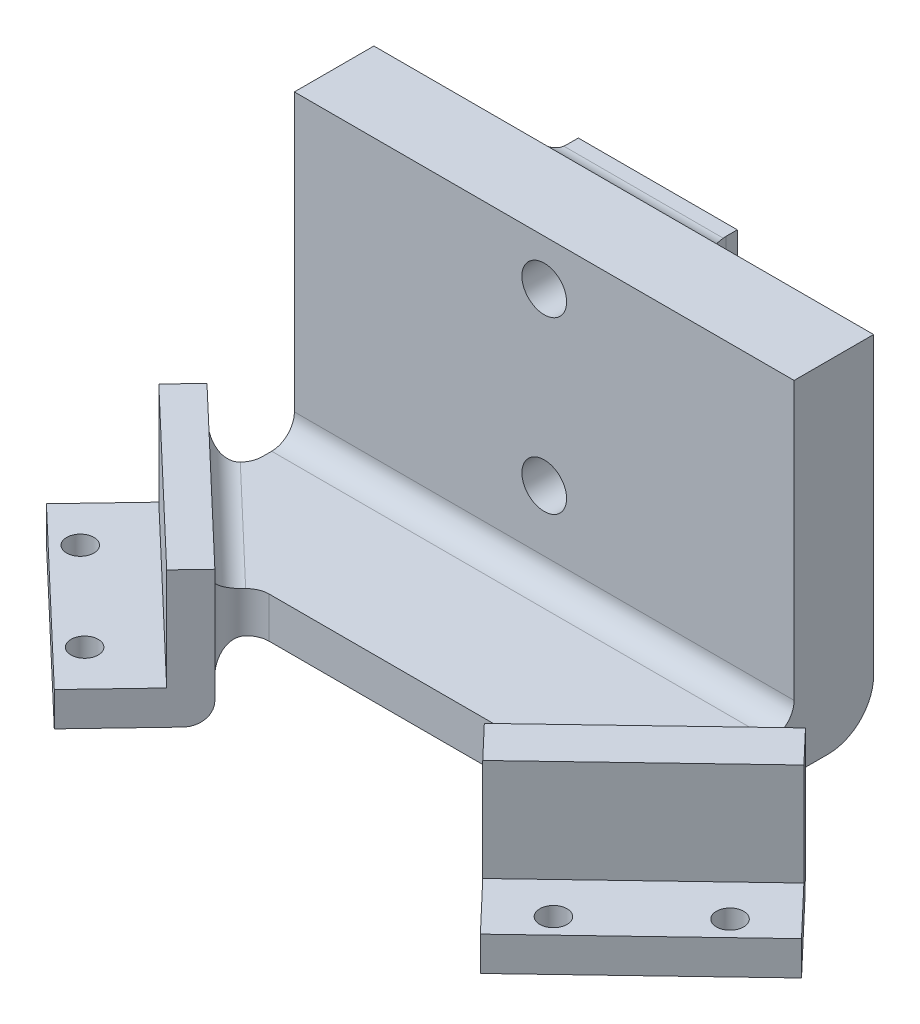
SolidWorks part; units mm, degrees
ref_plane "Front Plane" through (0, 0, 0) normal (0, 0, 1) x (1, 0, 0)
ref_plane "Top Plane" through (0, 0, 0) normal (0, 1, 0) x (1, 0, 0)
ref_plane "Right Plane" through (0, 0, 0) normal (1, 0, 0) x (0, 0, -1)
sketch "Sketch1" plane through (0, 0, 0) normal (0, 0, 1) x (1, 0, 0)
  line L0 (0, 89.7562) -> (0, -86.36) construction
  line L1 (27.94, 10.688) -> (-27.94, 10.688)
  line L2 (-27.94, 10.688) -> (-27.94, -27.412)
  line L3 (-27.94, -27.412) -> (27.94, -27.412)
  line L4 (27.94, 10.688) -> (27.94, -27.412)
  line L5 (-27.94, -22.84) -> (0, -22.84)
  line L6 (0, -22.84) -> (27.94, -22.84)
  line L7 (8.89, 9.3984) -> (-8.89, 9.3984)
  line L8 (-8.89, 9.3984) -> (-8.89, -19.8116)
  line L9 (-8.89, -19.8116) -> (8.89, -19.8116)
  line L10 (8.89, 9.3984) -> (8.89, -19.8116)
  line L11 (27.94, -22.84) -> (-27.94, -22.84) construction
  circle A0 centre (0, 5.5765) radius 2.5006
  circle A2 centre (0, -13.4735) radius 2.5006
  point P5 (-27.94, -8.362)
  point P7 (0, 10.688)
  point P8 (27.94, -8.362)
  point P11 (0, -27.412)
  point P19 (0, -19.8116)
  point P20 (0, 9.3984)
  dimension "D6" = 5.0013
  dimension "D7" = 5.0013
  dimension "D1" = 38.1
  dimension "D2" = 55.88
  dimension "D3" = 4.572
  dimension "D4" = 17.78
  dimension "D5" = 29.21
  dimension "D8" = 19.05
extrude "Boss-Extrude1" add sketch "Sketch1" along normal blind 8.89 contours L1 L0 L7 L10 L9 L6 L4 | L0 L1 L2 L5 L9 L8 L7 region at (17.623, -6.4095, 0) region at (-17.623, -6.4095, 0)
extrude "Boss-Extrude2" add sketch "Sketch1<3>" along normal blind 25.4 contours L6 L0 L3 L4 | L0 L5 L2 L3 region at (13.97, -25.126, 0) region at (-13.97, -25.126, 0)
sketch "Sketch1<3>" plane through (0, 0, 0) normal (0, 0, 1) x (1, 0, 0) same geometry as "Sketch1"
extrude "Boss-Extrude3" add sketch "Sketch1<4>" along normal blind 8.89 contours L0 L7 L8 L9 A2 A0 | L7 L0 A0 A2 L9 L10 region at (4.7219, -5.3095, 0) region at (-4.7219, -5.3095, 0)
sketch "Sketch1<4>" plane through (0, 0, 0) normal (0, 0, 1) x (1, 0, 0) same geometry as "Sketch1"
extrude "Boss-Extrude5" add sketch "Sketch1<5>" against normal blind 3.81 contours L0 L7 L8 L9 A2 A0 | L7 L0 A0 A2 L9 L10 region at (4.7219, -5.3095, 0) region at (-4.7219, -5.3095, 0)
sketch "Sketch1<5>" plane through (0, 0, 0) normal (0, 0, 1) x (1, 0, 0) same geometry as "Sketch1"
fillet "Fillet1" radius 2.54 1 edges at (0, 9.3984, 0)
fillet "Fillet7" radius 2.54 1 edges at (0, -19.8116, 0)
fillet "Fillet8" radius 2.54 1 edges at (-8.89, -5.8318, 0)
fillet "Fillet9" radius 2.54 1 edges at (8.89, -5.8318, 0)
fillet "Fillet10" radius 2.54 1 edges at (0, -22.84, 8.89)
fillet "Fillet12" radius 5.08 1 edges at (0, -27.412, 0)
sketch "Sketch2" plane through (0, -22.84, 0) normal (0, 1, 0) x (1, 0, 0)
  line L0 (0, -9.6533) -> (0, -27.4773)
  line L1 (-27.94, -18.415) -> (-20.6033, -25.4)
  line L2 (-27.94, -25.4) -> (-27.94, -11.43) construction
  line L3 (-20.6033, -25.4) -> (-27.94, -25.4)
  line L4 (-27.94, -25.4) -> (27.94, -25.4) construction
  line L5 (-27.94, -25.4) -> (-27.94, -18.415)
  line L6 (27.94, -25.4) -> (27.94, -18.415)
  line L7 (20.6033, -25.4) -> (27.94, -25.4)
  line L8 (27.94, -18.415) -> (20.6033, -25.4)
  line M2 (27.94, -25.4) -> (27.94, -11.43)
  line M4 (-27.94, -11.43) -> (-27.94, -25.4)
  line M5 (-27.94, -25.4) -> (27.94, -25.4)
extrude "Cut-Extrude1" cut sketch "Sketch2" against normal through all both and the other way through all contours L1 M4 M5 | L8 M2 M5 region at (25.4944, -22.84, 23.0717) region at (-25.4944, -22.84, 23.0717)
sketch "Sketch3" plane through (-22.4807, 0, 23.6126) normal (-0.6895, 0, 0.7243) x (0.7243, 0, 0.6895)
  line L0 (-2.0594, -15.8031) -> (-2.0594, -34.2191) construction
  line L1 (10.6711, -17.9031) -> (-14.7898, -17.9031)
  line L2 (-14.7898, -17.9031) -> (-14.7898, -33.1473)
  line L3 (-14.7898, -33.1473) -> (10.6711, -33.1473)
  line L4 (10.6711, -17.9031) -> (10.6711, -33.1473)
  line L5 (-14.7898, -29.3373) -> (-2.0594, -29.3373)
  line L6 (-2.0594, -29.3373) -> (10.6711, -29.3373)
  point P7 (-2.0594, -33.1473)
  point P8 (-2.0594, -17.9031)
  line M8 (-7.5378, -22.84) -> (-7.5378, -27.412)
  line M9 (-7.5378, -27.412) -> (2.5922, -27.412)
  line M10 (2.5922, -27.412) -> (2.5922, -22.84)
  line M11 (2.5922, -22.84) -> (-7.5378, -22.84)
  dimension "D1" = 3.81
  dimension "D2" = 25.4609
  dimension "D3" = 15.2442
sketch "Sketch4" plane through (22.4807, 0, 23.6126) normal (0.6895, 0, 0.7243) x (0.7243, 0, -0.6895)
  line L0 (2.4728, -13.3297) -> (2.4728, -37.4581) construction
  line L5 (15.1728, -18.0711) -> (-10.2272, -18.0711)
  line L6 (-10.2272, -18.0711) -> (-10.2272, -33.3111)
  line L7 (-10.2272, -33.3111) -> (15.1728, -33.3111)
  line L8 (-10.2272, -29.5011) -> (15.1728, -29.5011)
  line L9 (15.1728, -18.0711) -> (15.1728, -33.3111)
  point P7 (2.4728, -35.6165)
  point P8 (2.4728, -20.3765)
  point P11 (2.4728, -29.5011)
  point P12 (2.4728, -33.3111)
  point P13 (2.4728, -18.0711)
  line M7 (7.5378, -22.84) -> (-2.5922, -22.84)
  line M8 (-2.5922, -22.84) -> (-2.5922, -27.412)
  line M9 (-2.5922, -27.412) -> (7.5378, -27.412)
  line M10 (7.5378, -27.412) -> (7.5378, -22.84)
  dimension "D1" = 3.81
extrude "Boss-Extrude6" add sketch "Sketch3" along normal blind 3.81 contours L0 L1 L2 L5 M9 M8 M11 | L1 L0 L6 L4 M11 M10 M9 | L0 M11 M8 M9 | L0 M11 M9 M10 region at (-18.8617, -23.3626, 27.0582) region at (-29.1281, -23.3073, 17.2839) region at (-22.2878, -25.126, 23.7963) region at (-25.9561, -25.126, 20.3038)
extrude "Boss-Extrude7" add sketch "Sketch3<3>" along normal blind 12.7 contours L0 L5 L2 L3 | L6 L0 L3 L4 region at (-19.3622, -31.2423, 26.5816) region at (-28.5823, -31.2423, 17.8035)
sketch "Sketch3<3>" plane through (-22.4807, 0, 23.6126) normal (-0.6895, 0, 0.7243) x (0.7243, 0, 0.6895) same geometry as "Sketch3"
extrude "Boss-Extrude8" add sketch "Sketch4" along normal blind 5.08 contours L0 L5 L6 L8 M9 M8 M7 | L5 L0 L8 L9 M7 M10 M9 | L0 M7 M9 M10 | L0 M7 M8 M9 region at (29.3954, -23.5318, 17.0293) region at (19.1479, -23.5318, 26.7857) region at (26.1058, -25.126, 20.1613) region at (22.4375, -25.126, 23.6538)
extrude "Boss-Extrude9" add sketch "Sketch4<3>" along normal blind 12.7 contours L0 L8 L6 L7 | L8 L0 L7 L9 region at (28.8707, -31.4061, 17.5289) region at (19.6727, -31.4061, 26.2861)
sketch "Sketch4<3>" plane through (22.4807, 0, 23.6126) normal (0.6895, 0, 0.7243) x (0.7243, 0, -0.6895) same geometry as "Sketch4"
sketch "Sketch5" plane through (0, -29.3373, 0) normal (0, 1, 0) x (1, 0, 0)
  line L0 (-26.5994, -24.952) -> (-21.8389, -19.9518)
  line L1 (-35.8194, -16.1739) -> (-17.3793, -33.7301) construction
  line L2 (-21.8389, -19.9518) -> (-34.9251, -33.6968) construction
  line L3 (-41.9494, -22.6125) -> (-23.5093, -40.1687) construction
  line L4 (-23.5093, -40.1687) -> (-17.3793, -33.7301) construction
  circle A1 centre (-36.0368, -24.7346) radius 1.524
  circle A2 centre (-25.919, -34.3674) radius 1.524
  dimension "D1" = 3.048
  dimension "D2" = 13.97
  dimension "D3" = 2.54
  dimension "D4" = 5.7455
extrude "Cut-Extrude3" cut sketch "Sketch5" against normal blind 12.7 contours A1 | A2 region at (-36.0368, -29.3373, 24.7346) region at (-25.919, -29.3373, 34.3674)
sketch "Sketch7" plane through (0, -29.5011, 0) normal (0, 1, 0) x (1, 0, 0)
  line L0 (25.8936, -23.6111) -> (36.4503, -34.6993) construction
  line L1 (23.8308, -39.8626) -> (18.5765, -34.3438) construction
  line L2 (23.8308, -39.8626) -> (42.2268, -22.3484) construction
  circle A3 centre (26.2184, -34.0823) radius 1.524
  circle A4 centre (36.3362, -24.4495) radius 1.524
  dimension "D1" = 3.048
  dimension "D2" = 13.97
  dimension "D3" = 5.715
  dimension "D4" = 2.54
extrude "Cut-Extrude4" cut sketch "Sketch7" against normal through all both and the other way through all contours A3 | A4
fillet "Fillet14" radius 2.54 2 edges at (-24.2717, -27.412, 21.9075) (24.2717, -27.412, 21.9075)
fillet "Fillet15" radius 2.54 2 edges at (-24.2717, -22.84, 21.9075) (-27.94, -26.396, 18.415)
fillet "Fillet16" radius 2.54 2 edges at (27.94, -26.396, 18.415) (24.2717, -22.84, 21.9075)
fillet "Fillet17" radius 2.54 1 edges at (-20.6033, -25.126, 25.4)
fillet "Fillet18" radius 2.54 1 edges at (20.6033, -25.126, 25.4)
fillet "Fillet19" radius 2.54 2 edges at (-23.9722, -33.1473, 22.1926) (24.2717, -33.3111, 21.9075)
